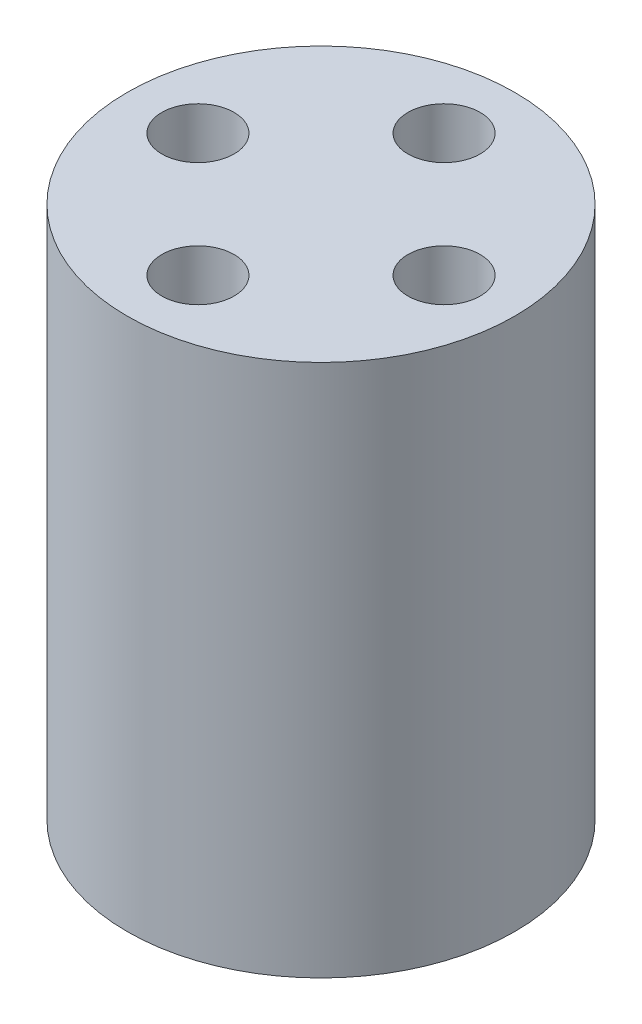
SolidWorks part; units mm, degrees
ref_plane "Front Plane" through (0, 0, 0) normal (0, 0, 1) x (1, 0, 0)
ref_plane "Top Plane" through (0, 0, 0) normal (0, 1, 0) x (1, 0, 0)
ref_plane "Right Plane" through (0, 0, 0) normal (1, 0, 0) x (0, 0, -1)
ref_axis "Axis1" through (0, 11.3464, 0) along (0, -1, 0)
sketch "Sketch2" plane through (0, 0, 0) normal (0, 1, 0) x (1, 0, 0)
  circle A0 centre (0, 0) radius 7.5
  dimension "D1" = 15
extrude "Boss-Extrude1" add sketch "Sketch2" along normal mid plane 20.6299
sketch "Sketch3" plane through (0, 0, 0) normal (0, 1, 0) x (1, 0, 0)
  circle A0 centre (0, 4.7625) radius 1.397
  point P2 (0, 0)
  point P4 (0, 0)
  dimension "D2" = 2.794
  dimension "D1" = 4.7625
extrude "Cut-Extrude1" cut sketch "Sketch3" against normal through all both and the other way through all
pattern_circular "CirPattern1" count 4 over 360 about axis through (0, 11.3464, 0) along (0, -1, 0) of "Cut-Extrude1"
